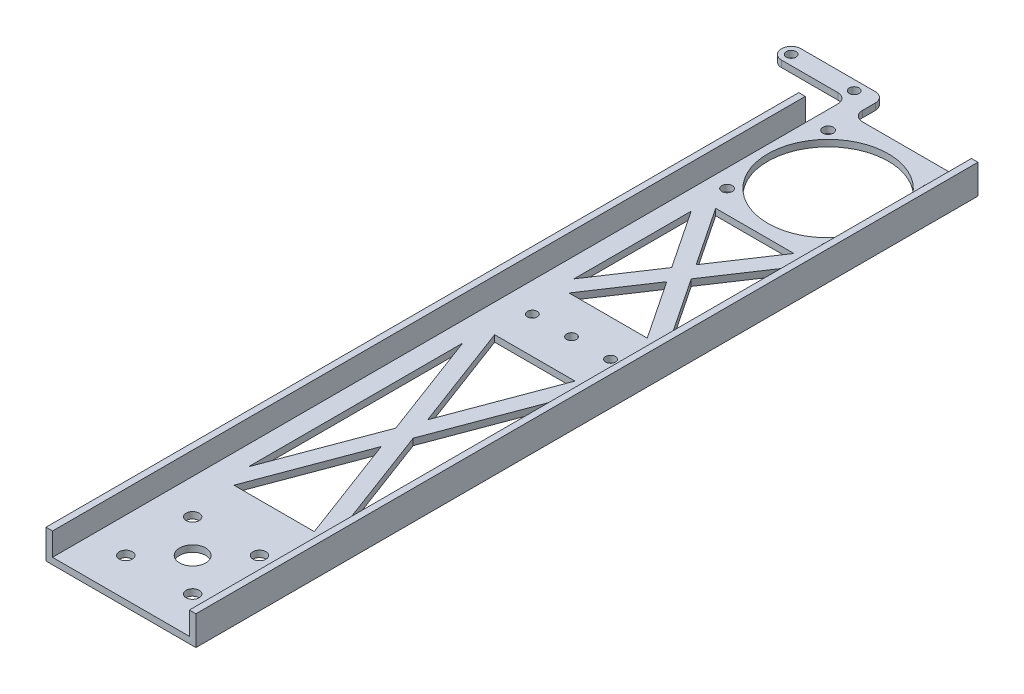
SolidWorks part; units mm, degrees
ref_plane "前视基准面" through (0, 0, 0) normal (0, 0, 1) x (1, 0, 0)
ref_plane "上视基准面" through (0, 0, 0) normal (0, 1, 0) x (1, 0, 0)
ref_plane "右视基准面" through (0, 0, 0) normal (1, 0, 0) x (0, 0, -1)
other "Configuration Table"
sketch "草图2" plane through (0, 0, 0) normal (0, 1, 0) x (1, 0, 0)
  line L1 (-21, -23) -> (21, -23)
  line L2 (-21, -23) -> (-21, 23)
  line L3 (-21, 23) -> (21, 23)
  line L4 (21, -23) -> (21, 23)
  line L5 (-21, -23) -> (21, 23) construction
  line L6 (-21, 23) -> (21, -23) construction
  circle A0 centre (0, 0) radius 18.5
extrude "凸台-拉伸1" add sketch "草图2" along normal blind 2
fillet "圆角1" radius 5.5 1 edges at (-21, 1, -23)
sketch "草图3" plane through (0, 2, 0) normal (0, 1, 0) x (1, 0, 0)
  line L1 (-15.5, -15.5) -> (15.5, -15.5)
  line L2 (-15.5, -15.5) -> (-15.5, 15.5)
  line L3 (-15.5, 15.5) -> (15.5, 15.5)
  line L4 (15.5, -15.5) -> (15.5, 15.5)
  line L5 (-15.5, -15.5) -> (15.5, 15.5) construction
  line L6 (-15.5, 15.5) -> (15.5, -15.5) construction
  circle A0 centre (-15.5, 15.5) radius 1.6
  circle A1 centre (15.5, 15.5) radius 1.6
  circle A2 centre (-15.5, -15.5) radius 1.6
  circle A3 centre (15.5, -15.5) radius 1.6
  point P0 (0, 0)
extrude "切除-拉伸1" cut sketch "草图3" against normal through all contours A2 | A0 | A1 | A3
sketch "草图4" plane through (0, 2, 0) normal (0, 1, 0) x (1, 0, 0)
  line L1 (-21, -23) -> (21, -23)
  line L4 (21, -176) -> (21, -23)
  line L5 (-21, -23) -> (-21, -176)
  line L11 (-10.253, -205.253) -> (10.253, -184.747) construction
  line L12 (-10.253, -184.747) -> (10.253, -205.253) construction
  line L14 (-21, -176) -> (-21, -217)
  line L15 (-21, -217) -> (21, -217)
  line L16 (21, -176) -> (21, -217)
  line L17 (21, -23) -> (21, 23) construction
  line L18 (-21, -23) -> (21, -23) construction
  circle A1 centre (0, -195) radius 4
  circle A3 centre (10.253, -184.747) radius 2
  circle A4 centre (-10.253, -184.747) radius 2
  circle A5 centre (10.253, -205.253) radius 2
  circle A6 centre (-10.253, -205.253) radius 2
  point P18 (0, -195)
  point P19 (0, -195)
extrude "凸台-拉伸2" add sketch "草图4" against normal blind 2
sketch "草图7" plane through (0, 2, 0) normal (0, 1, 0) x (1, 0, 0)
  line L13 (-21, 17.5) -> (-21, -217) construction
  line L14 (-15.5, 23) -> (-21, 17)
  line L15 (-41.33, 33) -> (-15.5, 33)
  line L16 (-15.5, 33) -> (-15.5, 23)
  line L17 (-41.33, 27) -> (-21, 27)
  line L18 (-21, 27) -> (-21, 17)
  line L19 (-41.33, 33) -> (-44.33, 33)
  line L20 (-44.33, 33) -> (-44.33, 27)
  line L21 (-44.33, 27) -> (-41.33, 27)
  circle A0 centre (-41.33, 30) radius 1.5
  circle A1 centre (-22, 30) radius 1.5
  point P1 (-27.1587, 40.886)
  point P20 (-41.33, 30)
extrude "凸台-拉伸4" add sketch "草图7" against normal blind 2
sketch "草图9" plane through (0, 2, 0) normal (0, 1, 0) x (1, 0, 0)
  line L0 (-23, 14) -> (-23, -217)
  line L1 (-23, -217) -> (-21, -217)
  line L2 (-21, -217) -> (21, -217) construction
  line L3 (-21, -217) -> (-21, 14)
  line L4 (-21, 14) -> (-23, 14)
  line L5 (23, 23) -> (23, -217)
  line L6 (23, -217) -> (21, -217)
  line L7 (21, -217) -> (21, 23)
  line L8 (21, 23) -> (-15.5, 23) construction
  line L9 (21, 23) -> (23, 23)
extrude "凸台-拉伸5" add sketch "草图9" along normal blind 7 and the other way blind 2
sketch "草图12" plane through (0, 2, 0) normal (0, 1, 0) x (1, 0, 0)
  line L1 (-15, -22.5) -> (15, -22.5)
  line L2 (-15, -22.5) -> (-15, -67.5)
  line L3 (-15, -67.5) -> (15, -67.5)
  line L4 (15, -22.5) -> (15, -67.5)
  line L5 (-15, -90) -> (15, -90)
  line L6 (-15, -90) -> (-15, -170)
  line L7 (-15, -170) -> (15, -170)
  line L8 (15, -90) -> (15, -170)
extrude "切除-拉伸4" cut sketch "草图12" against normal through all
sketch "草图13" plane through (0, 2, 0) normal (0, 1, 0) x (1, 0, 0)
  line L1 (-17.0801, -23.8868) -> (12.9199, -68.8868)
  line L2 (-17.0801, -23.8868) -> (-12.9199, -21.1132)
  line L3 (12.9199, -68.8868) -> (17.0801, -66.1132)
  line L4 (-12.9199, -21.1132) -> (17.0801, -66.1132)
  line L5 (-17.0801, -23.8868) -> (17.0801, -66.1132) construction
  line L6 (12.9199, -68.8868) -> (-12.9199, -21.1132) construction
  line L8 (-17.3408, -90.8778) -> (12.6592, -170.8778)
  line L9 (-17.3408, -90.8778) -> (-12.6592, -89.1222)
  line L10 (12.6592, -170.8778) -> (17.3408, -169.1222)
  line L11 (-12.6592, -89.1222) -> (17.3408, -169.1222)
  line L12 (-17.3408, -90.8778) -> (17.3408, -169.1222) construction
  line L13 (12.6592, -170.8778) -> (-12.6592, -89.1222) construction
  point P5 (0, -45)
  point P14 (0, -130)
extrude "凸台-拉伸6" add sketch "草图13" against normal blind 2
sketch "草图14" plane through (0, 2, 0) normal (0, 1, 0) x (1, 0, 0)
  line L1 (-17.0801, -66.1132) -> (12.9199, -21.1132)
  line L2 (-17.0801, -66.1132) -> (-12.9199, -68.8868)
  line L3 (12.9199, -21.1132) -> (17.0801, -23.8868)
  line L4 (-12.9199, -68.8868) -> (17.0801, -23.8868)
  line L5 (-17.0801, -66.1132) -> (17.0801, -23.8868) construction
  line L6 (12.9199, -21.1132) -> (-12.9199, -68.8868) construction
  line L7 (-17.3408, -169.1222) -> (12.6592, -89.1222)
  line L8 (-17.3408, -169.1222) -> (-12.6592, -170.8778)
  line L9 (12.6592, -89.1222) -> (17.3408, -90.8778)
  line L10 (-12.6592, -170.8778) -> (17.3408, -90.8778)
  line L11 (-17.3408, -169.1222) -> (17.3408, -90.8778) construction
  line L12 (12.6592, -89.1222) -> (-12.6592, -170.8778) construction
  point P5 (0, -45)
  point P6 (0, -130)
extrude "凸台-拉伸7" add sketch "草图14" against normal blind 2
fillet "圆角2" radius 3 5 edges at (-15.5, 1, -23) (-15.5, 1, -33) (-21, 1, -27) (-44.33, 1, -27) (-44.33, 1, -33)
sketch "草图15" plane through (0, 2, 0) normal (0, 1, 0) x (1, 0, 0)
  circle A0 centre (0, -78.75) radius 1.5
  circle A1 centre (12, -78.75) radius 1.5
  circle A2 centre (-12, -78.75) radius 1.5
  point P9 (0, -78.75)
extrude "切除-拉伸5" cut sketch "草图15" against normal through all
